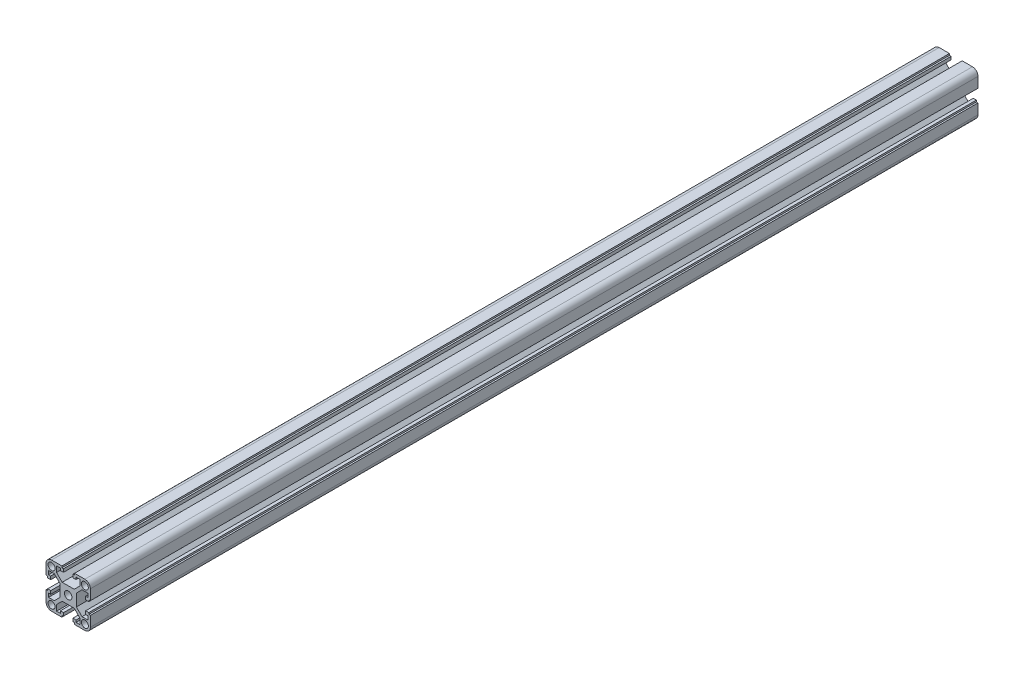
SolidWorks part; units mm, degrees
material "АД1 ГОСТ 4784-97"
ref_plane "Спереди" through (0, 0, 0) normal (0, 0, 1) x (1, 0, 0)
ref_plane "Сверху" through (0, 0, 0) normal (0, 1, 0) x (1, 0, 0)
ref_plane "Справа" through (0, 0, 0) normal (1, 0, 0) x (0, 0, -1)
ref_axis "ОсьX" through (-88.99, 0, 0) along (1, 0, 0)
ref_axis "ОсьZ" through (0, 55, 0) along (0, -1, 0)
ref_axis "ОсьY" through (0, 0, -88.99) along (0, 0, 1)
sketch "Эскиз1" plane through (0, 0, 0) normal (0, 0, 1) x (1, 0, 0)
  line L0 (-15, 20) -> (-5.7274, 20)
  line L1 (-5.7274, 20) -> (-5.7274, 18.5304)
  line L2 (-5.7274, 18.5304) -> (-4.25, 18.5304)
  line L3 (-4.25, 18.5304) -> (-4.25, 15.732)
  line L4 (-4.25, 15.732) -> (-7.1118, 15.732)
  line L5 (-7.1118, 15.732) -> (-7.1118, 17.7)
  line L6 (-7.1118, 17.7) -> (-10.5, 17.7)
  line L7 (-10.5, 17.7) -> (-10.5, 12.4799)
  line L8 (-10.5, 12.4799) -> (-5.4201, 7.4)
  line L9 (-20, 15) -> (-20, 5.7274)
  line L10 (0, 0) -> (0, 8.4096) construction
  line L11 (-15, 15) -> (0, 0) construction
  line L12 (10.5, 12.4799) -> (5.4201, 7.4)
  line L13 (10.5, 17.7) -> (10.5, 12.4799)
  line L14 (7.1118, 17.7) -> (10.5, 17.7)
  line L15 (7.1118, 15.732) -> (7.1118, 17.7)
  line L16 (4.25, 15.732) -> (7.1118, 15.732)
  line L17 (4.25, 18.5304) -> (4.25, 15.732)
  line L18 (5.7274, 18.5304) -> (4.25, 18.5304)
  line L19 (5.7274, 20) -> (5.7274, 18.5304)
  line L20 (15, 20) -> (5.7274, 20)
  line L21 (-5.4201, 7.4) -> (5.4201, 7.4)
  line L22 (-8.8445, 0) -> (0, 0) construction
  line L23 (-12.4799, 10.5) -> (-7.4, 5.4201)
  line L24 (-17.7, 10.5) -> (-12.4799, 10.5)
  line L25 (-17.7, 7.1118) -> (-17.7, 10.5)
  line L26 (-15.732, 7.1118) -> (-17.7, 7.1118)
  line L27 (-15.732, 4.25) -> (-15.732, 7.1118)
  line L28 (-18.5304, 4.25) -> (-15.732, 4.25)
  line L29 (-18.5304, 5.7274) -> (-18.5304, 4.25)
  line L30 (-20, 5.7274) -> (-18.5304, 5.7274)
  line L31 (18.5304, 5.7274) -> (18.5304, 4.25)
  line L32 (18.5304, 4.25) -> (15.732, 4.25)
  line L33 (15.732, 4.25) -> (15.732, 7.1118)
  line L34 (15.732, 7.1118) -> (17.7, 7.1118)
  line L35 (12.4799, 10.5) -> (7.4, 5.4201)
  line L36 (17.7, 10.5) -> (12.4799, 10.5)
  line L37 (17.7, 7.1118) -> (17.7, 10.5)
  line L38 (20, 5.7274) -> (18.5304, 5.7274)
  line L39 (20, 15) -> (20, 5.7274)
  line L40 (20, -15) -> (20, -5.7274)
  line L41 (20, -5.7274) -> (18.5304, -5.7274)
  line L42 (17.7, -7.1118) -> (17.7, -10.5)
  line L43 (17.7, -10.5) -> (12.4799, -10.5)
  line L44 (12.4799, -10.5) -> (7.4, -5.4201)
  line L45 (15.732, -7.1118) -> (17.7, -7.1118)
  line L46 (15.732, -4.25) -> (15.732, -7.1118)
  line L47 (18.5304, -4.25) -> (15.732, -4.25)
  line L48 (18.5304, -5.7274) -> (18.5304, -4.25)
  line L49 (-20, -5.7274) -> (-18.5304, -5.7274)
  line L50 (-18.5304, -5.7274) -> (-18.5304, -4.25)
  line L51 (-18.5304, -4.25) -> (-15.732, -4.25)
  line L52 (-15.732, -4.25) -> (-15.732, -7.1118)
  line L53 (-15.732, -7.1118) -> (-17.7, -7.1118)
  line L54 (-17.7, -7.1118) -> (-17.7, -10.5)
  line L55 (-17.7, -10.5) -> (-12.4799, -10.5)
  line L56 (-12.4799, -10.5) -> (-7.4, -5.4201)
  line L57 (-5.4201, -7.4) -> (5.4201, -7.4)
  line L58 (15, -20) -> (5.7274, -20)
  line L59 (5.7274, -20) -> (5.7274, -18.5304)
  line L60 (5.7274, -18.5304) -> (4.25, -18.5304)
  line L61 (4.25, -18.5304) -> (4.25, -15.732)
  line L62 (4.25, -15.732) -> (7.1118, -15.732)
  line L63 (7.1118, -15.732) -> (7.1118, -17.7)
  line L64 (7.1118, -17.7) -> (10.5, -17.7)
  line L65 (10.5, -17.7) -> (10.5, -12.4799)
  line L66 (10.5, -12.4799) -> (5.4201, -7.4)
  line L67 (-20, -15) -> (-20, -5.7274)
  line L68 (-10.5, -12.4799) -> (-5.4201, -7.4)
  line L69 (-10.5, -17.7) -> (-10.5, -12.4799)
  line L70 (-7.1118, -17.7) -> (-10.5, -17.7)
  line L71 (-7.1118, -15.732) -> (-7.1118, -17.7)
  line L72 (-4.25, -15.732) -> (-7.1118, -15.732)
  line L73 (-4.25, -18.5304) -> (-4.25, -15.732)
  line L74 (-5.7274, -18.5304) -> (-4.25, -18.5304)
  line L75 (-5.7274, -20) -> (-5.7274, -18.5304)
  line L76 (-15, -20) -> (-5.7274, -20)
  line L77 (-7.4, 5.4201) -> (-7.4, -5.4201)
  line L78 (7.4, 5.4201) -> (7.4, -5.4201)
  circle A0 centre (0, 0) radius 3.4
  circle A1 centre (-15, 15) radius 3.15
  arc A2 (-15, 20) -> (-20, 15) centre (-15, 15) ccw
  arc A3 (15, 20) -> (20, 15) centre (15, 15) cw
  circle A4 centre (15, 15) radius 3.15
  circle A5 centre (15, -15) radius 3.15
  arc A6 (15, -20) -> (20, -15) centre (15, -15) ccw
  arc A7 (-15, -20) -> (-20, -15) centre (-15, -15) cw
  circle A8 centre (-15, -15) radius 3.15
  dimension "D1" = 6.8
  dimension "D2" = 6.3
  dimension "D3" = 40
  dimension "D8" = 30
  dimension "D4" = 2.3
  dimension "D5" = 1.35
  dimension "D6" = 21
  dimension "D7" = 8.5
  dimension "D9" = 45
  dimension "D10" = 2.8
  dimension "D11" = 4
  dimension "D13" = 40
extrude "Бобышка-Вытянуть1" add sketch "Эскиз1" along normal mid plane 800
